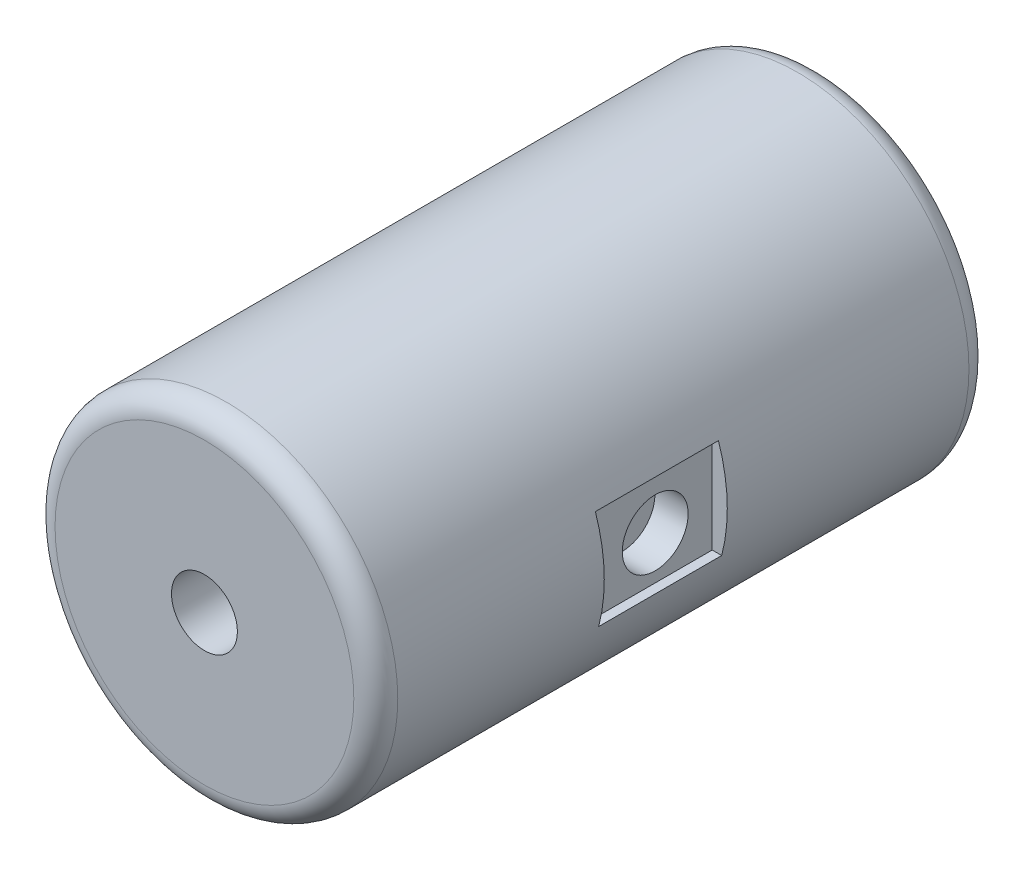
SolidWorks part; units mm, degrees
ref_plane "Front Plane" through (0, 0, 0) normal (0, 0, 1) x (1, 0, 0)
ref_plane "Top Plane" through (0, 0, 0) normal (0, 1, 0) x (1, 0, 0)
ref_plane "Right Plane" through (0, 0, 0) normal (1, 0, 0) x (0, 0, -1)
sketch "Sketch1" plane through (0, 0, 0) normal (0, 0, 1) x (1, 0, 0)
  circle A0 centre (0, 0) radius 3.9
  dimension "D1" = 7.8
extrude "Boss-Extrude1" add sketch "Sketch1" along normal blind 14
fillet "Fillet1" radius 0.5 2 edges at (3.9, 0, 0) (3.9, 0, 14)
sketch "Sketch2" plane through (0, 0, 14) normal (0, 0, 1) x (1, 0, 0)
  circle A2 centre (0, 0) radius 0.75
  dimension "D1" = 1.5
extrude "Cut-Extrude2" cut sketch "Sketch2" against normal blind 5
sketch "Sketch3" plane through (0, 0, 0) normal (0, 0, -1) x (-1, 0, 0)
  circle A0 centre (0, 1.5) radius 0.75
  circle A1 centre (0, -1.5) radius 0.75
  dimension "D2" = 1.5
  dimension "D3" = 1.5
  dimension "D1" = 1.5
  dimension "D4" = 1.5
extrude "Cut-Extrude3" cut sketch "Sketch3" against normal blind 5
ref_plane "Plane1" through (-3.8, 0, 0) normal (1, 0, 0) x (0, 0, -1)
sketch "Sketch4" plane through (-3.8, 0, 0) normal (1, 0, 0) x (0, 0, -1)
  circle A0 centre (-7.2972, 0) radius 0.75
  dimension "D1" = 1.5
extrude "Cut-Extrude4" cut sketch "Sketch4" along normal blind 1 and the other way blind 1
ref_plane "Plane2" through (0, 0, 6) normal (0, 0, 1) x (1, 0, 0)
sketch "Sketch5" plane through (0, 0, 6) normal (0, 0, 1) x (1, 0, 0)
  line L1 (-3.5566, 1.2391) -> (-3.9916, 1.2391)
  line L2 (-3.5566, 1.2391) -> (-3.5566, -0.9889)
  line L3 (-3.5566, -0.9889) -> (-3.9916, -0.9889)
  line L4 (-3.9916, 1.2391) -> (-3.9916, -0.9889)
  line L5 (-3.5566, 1.2391) -> (-3.9916, -0.9889) construction
  line L6 (-3.5566, -0.9889) -> (-3.9916, 1.2391) construction
  point P4 (-3.7741, 0.1251)
extrude "Cut-Extrude5" cut sketch "Sketch5" along normal blind 2.8
mirror "Mirror1" about plane through (0, 0, 0) normal (1, 0, 0) of "Cut-Extrude5", "Cut-Extrude4"
